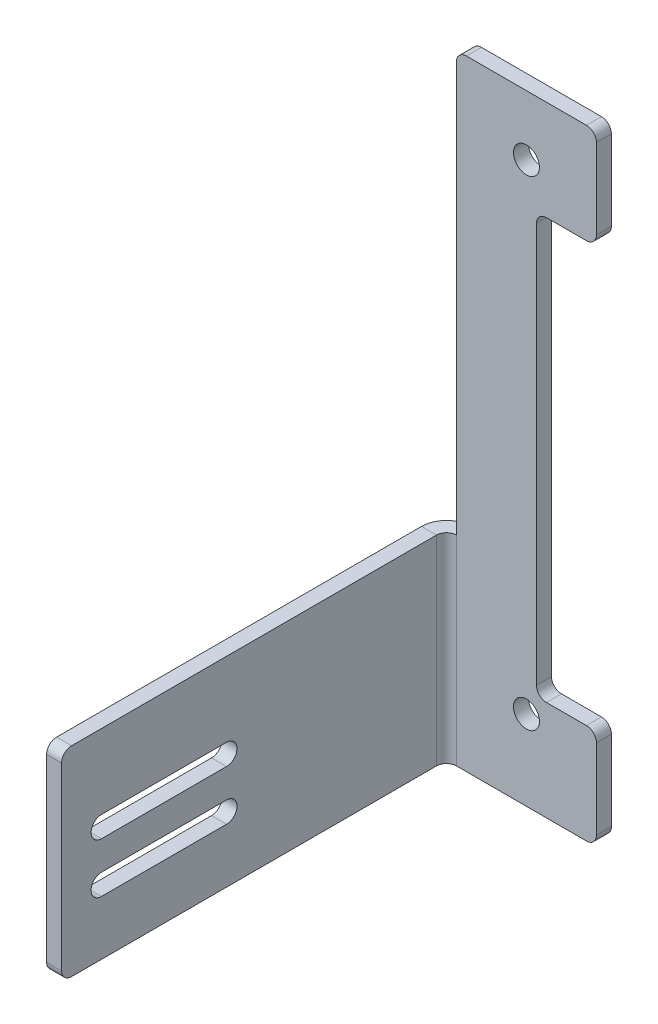
SolidWorks part; units mm, degrees
note: The reader was unsure of these and kept them because the rebuilt part matched: flange length of "Odgięcie krawędzi1".
ref_plane "Płaszczyzna przednia" through (0, 0, 0) normal (0, 0, 1) x (1, 0, 0)
ref_plane "Płaszczyzna górna" through (0, 0, 0) normal (0, 1, 0) x (1, 0, 0)
ref_plane "Płaszczyzna prawa" through (0, 0, 0) normal (1, 0, 0) x (0, 0, -1)
sketch "Szkic1" plane through (0, 0, 0) normal (0, 0, 1) x (1, 0, 0)
  line L0 (30, -42) -> (30, -62)
  line L1 (0, 62) -> (30, 62)
  line L2 (0, 62) -> (0, -62)
  line L3 (0, -62) -> (30, -62)
  line L4 (30, 62) -> (30, 42)
  line L5 (30, -42) -> (18, -42)
  line L7 (30, 42) -> (18, 42)
  line L8 (18, -42) -> (18, 42)
  dimension "D1" = 20
  dimension "D2" = 84
  dimension "D3" = 20
  dimension "D4" = 30
  dimension "D5" = 12
base flange "Odgięcie bazowe1" sketch "Szkic1" thickness 3 reverse thickness direction no parameters "D1"=2
edge flange "Odgięcie krawędzi1" sketch "Szkic8" flange angle 90 flange length 80 flange position material outside bend radius 2 thickness 3 relief rectangular parameters "D6"=10
sketch "Szkic8" plane through (0, 0, 0) normal (-1, 0, 0) x (0, -1, 0)
  line L0 (-62, 0) -> (62, 0) construction
  line L1 (-62, 0) -> (62, 0)
  line L2 (-62, 0) -> (-62, 77)
  line L3 (-62, 77) -> (62, 77)
  line L4 (62, 77) -> (62, 0)
bend "Zgięcie krawędziowe1" bend radius 2 bend angle 90 parameters "D5"=1
sketch "Szkic10" plane through (0, 62, 0) normal (0, 1, 0) x (1, 0, 0)
  line L0 (2, 0) -> (2, 3) construction
  line L1 (-3, -2) -> (-3, -77) construction
  line L2 (-3, -77) -> (0, -77) construction
  line L3 (0, -77) -> (0, -2) construction
  line L4 (2, 0) -> (2, 3)
  line L5 (-3, -2) -> (-3, -77)
  line L6 (-3, -77) -> (0, -77)
  line L7 (0, -77) -> (0, -2)
  arc A0 (2, 0) -> (0, -2) centre (2, -2) ccw construction
  arc A1 (2, 3) -> (-3, -2) centre (2, -2) ccw construction
  arc A2 (2, 0) -> (0, -2) centre (2, -2) ccw
  arc A3 (2, 3) -> (-3, -2) centre (2, -2) ccw
extrude "Wytnij-wyciągnięcie1" cut sketch "Szkic10" against normal blind 84 normal cut yes
hole_wizard "Otwór Ø5.2 (5.2)1" positions "Szkic 3D1" profile "Szkic11" hole size "Ø5.2" standard "Ansi Metric" end condition through all
sketch3d "Szkic 3D1"
  line L0 (18, 42, 0) -> (30, 42, 0) construction
  line L1 (30, 42, 0) -> (30, 62, 0) construction
  point P0 (16, -46, 0)
  point P2 (16, 50, 0)
  dimension "D1" = 96
  dimension "D2" = 8
  dimension "D3" = 14
sketch "Szkic11" plane through (16, -46, 0) normal (1, 0, 0) x (0, -1, 0)
  line L0 (0, 0) -> (0, 3)
  line L1 (0, 3) -> (2.6, 3)
  line L2 (2.6, 3) -> (2.6, 0)
  line L5 (2.6, 0) -> (0, 0)
  line L11 (0, -6.35) -> (0, 107.95) construction
  dimension "Średnica otworu na wylot" = 5.2
  dimension "Głębokość otworu na wylot" = 3
hole_wizard "Otwór Ø4.2 (4.2)1" positions "Szkic 3D2" profile "Szkic12" hole size "Ø4.2" standard "Ansi Metric" end condition through all
sketch3d "Szkic 3D2"
  line L0 (0, -62, 2) -> (0, -62, 77) construction
  line L1 (0, -62, 77) -> (0, -22, 77) construction
  point P0 (0, -49, 69)
  point P2 (0, -39, 69)
  dimension "D1" = 10
  dimension "D2" = 13
  dimension "D3" = 8
sketch "Szkic12" plane through (0, -49, 69) normal (0, 1, 0) x (0, 0, -1)
  line L0 (0, 0) -> (0, 3)
  line L1 (0, 3) -> (2.1, 3)
  line L2 (2.1, 3) -> (2.1, 0)
  line L5 (2.1, 0) -> (0, 0)
  line L11 (0, -6.35) -> (0, 107.95) construction
  dimension "Średnica otworu na wylot" = 4.2
  dimension "Głębokość otworu na wylot" = 3
sketch "Szkic14" plane through (0, 0, 0) normal (1, 0, 0) x (0, 0, -1)
  line L0 (-69, -49) -> (-44, -49) construction
  line L1 (-69, -46.9) -> (-44, -46.9)
  line L2 (-69, -51.1) -> (-44, -51.1)
  line L3 (-69, -39) -> (-44, -39) construction
  line L4 (-69, -36.9) -> (-44, -36.9)
  line L5 (-69, -41.1) -> (-44, -41.1)
  arc A0 (-69, -46.9) -> (-69, -51.1) centre (-69, -49) ccw
  arc A1 (-44, -51.1) -> (-44, -46.9) centre (-44, -49) ccw
  circle A2 centre (-69, -49) radius 2.1 construction
  arc A3 (-69, -36.9) -> (-69, -41.1) centre (-69, -39) ccw
  arc A4 (-44, -41.1) -> (-44, -36.9) centre (-44, -39) ccw
  circle A5 centre (-69, -39) radius 2.1 construction
  point P3 (-56.5, -49)
  point P13 (-56.5, -39)
  dimension "D1" = 25
extrude "Wytnij-wyciągnięcie2" cut sketch "Szkic14" against normal through all normal cut yes
fillet "Zaokrąglenie1" radius 2 9 edges at (30, -62, -1.5) (2, 62, -1.5) (30, 62, -1.5) (30, -42, -1.5) (-1.5, -62, 77) (-1.5, -22, 77) (18, 42, -1.5) (30, 42, -1.5) (18, -42, -1.5)
sketch "Linie zgięcia1" plane through (0, 0, 0) normal (0, 1, 0) x (1, 0, 0)
sketch "Ramka-graniczna1" plane through (0, 0, 0) normal (0, 1, 0) x (1, 0, 0)
sheet metal parameters "Arkusz blachy1" thickness 3 parameters "D1"=2
flat pattern "Rozłożony model1" [suppressed]
sketch "Linie zgięcia2" plane through (0, 0, 0) normal (0, 1, 0) x (1, 0, 0)
sketch "Ramka-graniczna2" [suppressed] plane through (0, 0, 0) normal (0, 1, 0) x (1, 0, 0)
sheet metal parameters "Arkusz blachy2" thickness 3 parameters "D1"=2
flat pattern "Rozłożony model1" [suppressed]
sketch "Linie zgięcia2" plane through (0, 0, 0) normal (0, 1, 0) x (1, 0, 0)
sketch "Ramka-graniczna2" [suppressed] plane through (0, 0, 0) normal (0, 1, 0) x (1, 0, 0)
bend of the flat pattern "Rozłożone-<Zgięcie krawędziowe1>1"
sheet metal parameters "Arkusz blachy3" thickness 3 parameters "D1"=2
flat pattern "Rozłożony model1" [suppressed]
sketch "Linie zgięcia2" plane through (0, 0, 0) normal (0, 1, 0) x (1, 0, 0)
sketch "Ramka-graniczna2" [suppressed] plane through (0, 0, 0) normal (0, 1, 0) x (1, 0, 0)
bend of the flat pattern "Rozłożone-<Zgięcie krawędziowe1>1"
sheet metal parameters "Arkusz blachy4" thickness 3 parameters "D1"=2
flat pattern "Rozłożony model1" [suppressed]
sketch "Linie zgięcia2" plane through (0, 0, 0) normal (0, 1, 0) x (1, 0, 0)
sketch "Ramka-graniczna2" [suppressed] plane through (0, 0, 0) normal (0, 1, 0) x (1, 0, 0)
bend of the flat pattern "Rozłożone-<Zgięcie krawędziowe1>1"
sheet metal parameters "Arkusz blachy5" thickness 3 parameters "D1"=2
flat pattern "Rozłożony model1" [suppressed]
sketch "Linie zgięcia2" plane through (0, 0, 0) normal (0, 1, 0) x (1, 0, 0)
sketch "Ramka-graniczna2" [suppressed] plane through (0, 0, 0) normal (0, 1, 0) x (1, 0, 0)
bend of the flat pattern "Rozłożone-<Zgięcie krawędziowe1>1"
sheet metal parameters "Arkusz blachy6" thickness 3 parameters "D1"=2
flat pattern "Rozłożony model1"
sketch "Linie zgięcia2" plane through (0, 0, 0) normal (0, 0, 1) x (1, 0, 0)
  line L0 (-0.7489, -22) -> (-0.7489, -62) construction
  line L1 (-0.7489, -22) -> (-0.7489, -62) construction
sketch3d "Ramka-graniczna2" [suppressed]
  line L0 (29.9999, -62, 0) -> (30, 62, 0) construction
  line L1 (-78.4978, -61.9999, 0) -> (-78.4977, 62.0001, 0) construction
  line L2 (29.9999, -62, 0) -> (-78.4978, -61.9999, 0) construction
  line L3 (30, 62, 0) -> (-78.4977, 62.0001, 0) construction
bend of the flat pattern "Rozłożone-<Zgięcie krawędziowe1>1"
